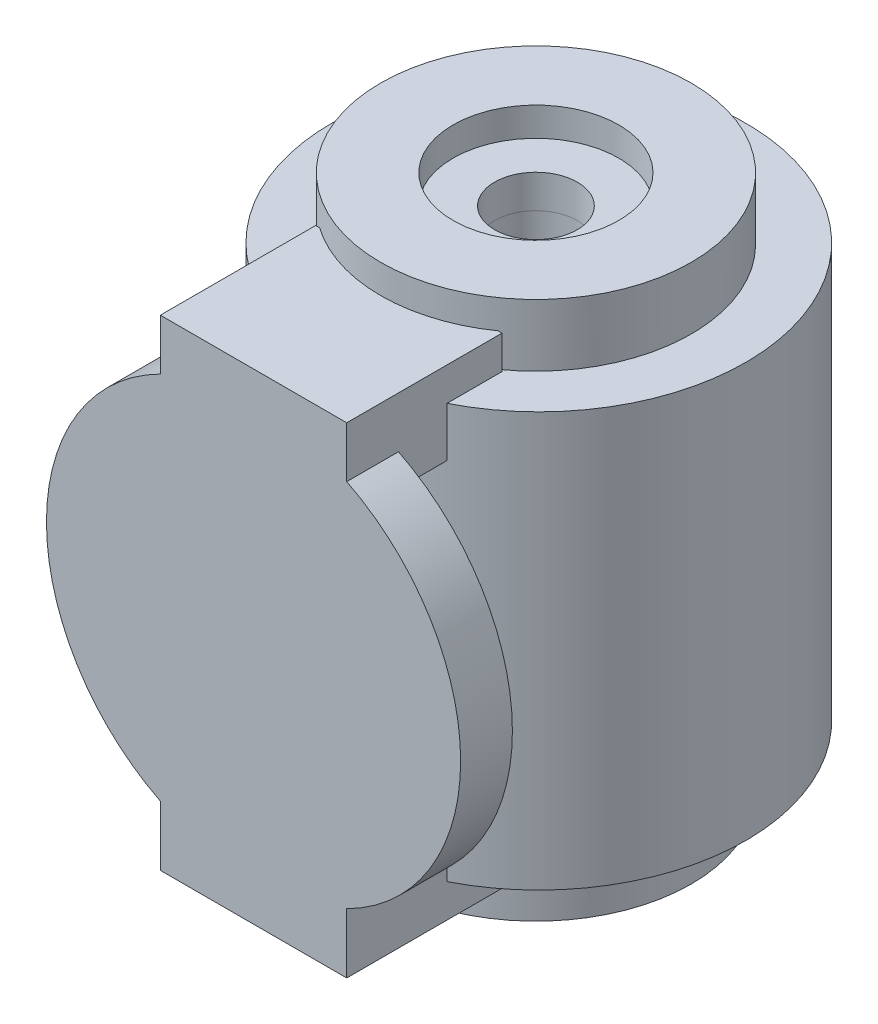
SolidWorks part; units mm, degrees
ref_plane "前视基准面" through (0, 0, 0) normal (0, 0, 1) x (1, 0, 0)
ref_plane "上视基准面" through (0, 0, 0) normal (0, 1, 0) x (1, 0, 0)
ref_plane "右视基准面" through (0, 0, 0) normal (1, 0, 0) x (0, 0, -1)
sketch "草图1" plane through (0, 0, 0) normal (0, 0, 1) x (1, 0, 0)
  circle A0 centre (0, 0) radius 20
extrude "凸台-拉伸1" add sketch "草图1" along normal blind 5
sketch "草图3" plane through (0, 0, 5) normal (0, 0, 1) x (1, 0, 0)
  line L1 (-9, -15.6525) -> (9, -15.6525)
  line L2 (-9, -15.6525) -> (-9, -23.6525)
  line L3 (-9, -23.6525) -> (9, -23.6525)
  line L4 (9, -15.6525) -> (9, -23.6525)
  line L6 (-9, 22.786) -> (9, 22.786)
  line L7 (9, 14.786) -> (9, 22.786)
  line L8 (-9, 14.786) -> (9, 14.786)
  line L9 (-9, 14.786) -> (-9, 22.786)
  point P7 (0, -15.6525)
  dimension "D1" = 18
  dimension "D2" = 8
extrude "凸台-拉伸2" add sketch "草图3" against normal blind 15
sketch "草图4" plane through (0, 14.786, 0) normal (0, -1, 0) x (1, 0, 0)
  circle A0 centre (0, -22.5472) radius 20
extrude "凸台-拉伸3" add sketch "草图4" along normal blind 35.22 and the other way blind 4.78
sketch "草图6" plane through (0, 19.566, 0) normal (0, 1, 0) x (1, 0, 0)
  circle A0 centre (0, 22.2721) radius 15
extrude "凸台-拉伸4" add sketch "草图6" along normal blind 6 and the other way blind 36.4385
sketch "草图10" plane through (0, 22.786, 0) normal (0, 1, 0) x (1, 0, 0)
  circle A1 centre (0, 22.2721) radius 8
  point P1 (0, 22.2721)
extrude "切除-拉伸1" cut sketch "草图10" along normal blind 6
sketch "草图11" plane through (0, -23.6525, 0) normal (0, -1, 0) x (1, 0, 0)
  circle A1 centre (0, -22.2721) radius 8
  point P1 (0, -22.2721)
sketch "草图14" plane through (0, -20.434, 0) normal (0, -1, 0) x (-1, 0, 0)
  circle A0 centre (0, 22.491) radius 20
  circle A1 centre (0, 22.2721) radius 15
extrude "凸台-拉伸6" add sketch "草图14" along normal blind 6 contours A1
extrude "切除-拉伸4" cut sketch "草图11" along normal blind 6
sketch "草图16" plane through (0, 22.786, 0) normal (0, 1, 0) x (1, 0, 0)
  circle A1 centre (0, 22.2721) radius 4
  point P1 (0, 22.2721)
extrude "切除-拉伸5" cut sketch "草图16" against normal blind 50
sketch "草图23" plane through (0, 22.786, 0) normal (0, 1, 0) x (1, 0, 0)
  circle A0 centre (0, 22.2721) radius 4.01
  circle A1 centre (0, 22.2721) radius 3.99
  point P0 (0, 22.2721)
extrude "凸台-拉伸7" add sketch "草图23" against normal blind 3.22
sketch "草图25" plane through (0, 0, 5) normal (0, 0, 1) x (1, 0, 0)
  point P0 (0, 0)
ref_point "点4"
sketch "草图26" plane through (0, 0, 5) normal (0, 0, 1) x (1, 0, 0)
  line L0 (0, 0) -> (0, 20)
ref_axis "基准轴3" through (0, 0, 5) along (0, 0, 1)
ref_axis "基准轴4" through (0, 0, 5) along (0, 1, 0)
ref_axis "基准轴5" through (0, -23.6525, -22.2721) along (0, 1, 0)
ref_point "点6"
ref_plane "基准面2" through (0, 0, -22.2721) normal (0, 0, -1) x (-1, 0, 0)
ref_axis "基准轴6" through (0, 0, -18.6623) along (0, 0, -1)
